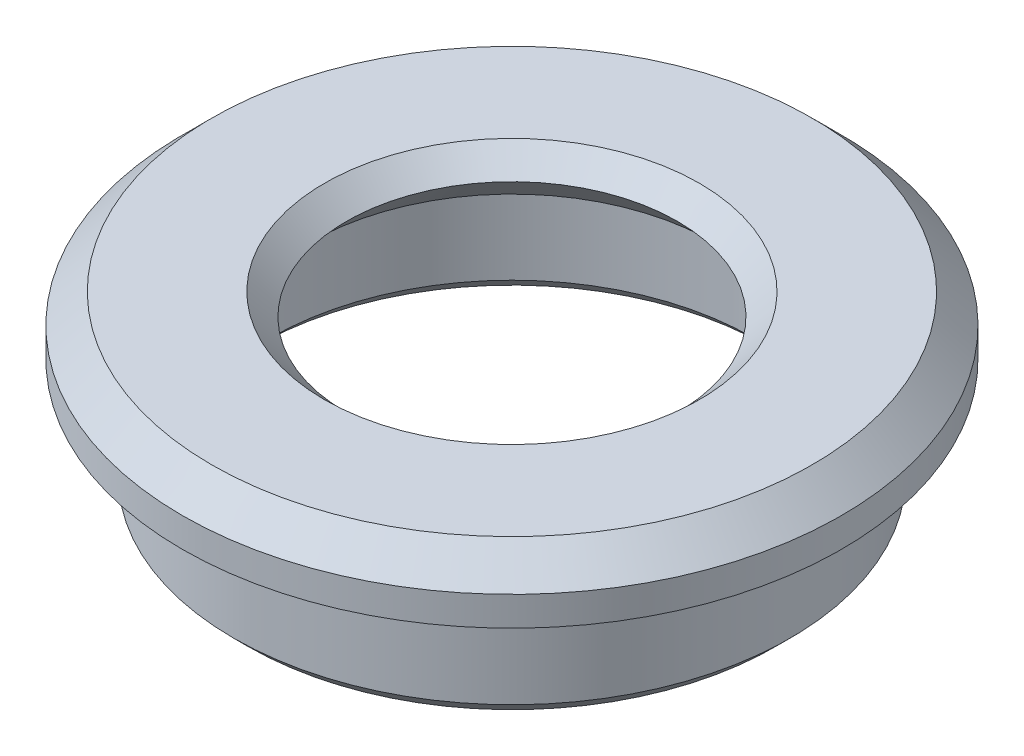
SolidWorks part; units mm, degrees
ref_plane "Front Plane" through (0, 0, 0) normal (0, 0, 1) x (1, 0, 0)
ref_plane "Top Plane" through (0, 0, 0) normal (0, 1, 0) x (1, 0, 0)
ref_plane "Right Plane" through (0, 0, 0) normal (1, 0, 0) x (0, 0, -1)
sketch "Sketch1" plane through (0, 0, 0) normal (0, 1, 0) x (1, 0, 0)
  circle A0 centre (0, 0) radius 8.25
  circle A1 centre (0, 0) radius 9.5
  dimension "D1" = 16.5
  dimension "D2" = 1.25
extrude "Boss-Extrude1" add sketch "Sketch1" along normal blind 4
sketch "Sketch2" plane through (0, 4, 0) normal (0, 1, 0) x (1, 0, 0)
  circle A0 centre (0, 0) radius 11.25
  dimension "D1" = 22.5
extrude "Boss-Extrude2" add sketch "Sketch2" along normal blind 2
sketch "Sketch3" plane through (0, 6, 0) normal (0, 1, 0) x (1, 0, 0)
  circle A0 centre (0, 0) radius 5.4
  dimension "D1" = 10.8
extrude "Cut-Extrude1" cut sketch "Sketch3" against normal through all both and the other way through all
chamfer "Chamfer1" distance 1.5 angle 45 1 edges at (0, 4, 5.4)
chamfer "Chamfer2" distance 0.5 angle 45 2 edges at (0, 0, 8.25) (0, 0, 9.5)
chamfer "Chamfer3" distance 1 angle 45 2 edges at (0, 6, 11.25) (0, 6, 5.4)
